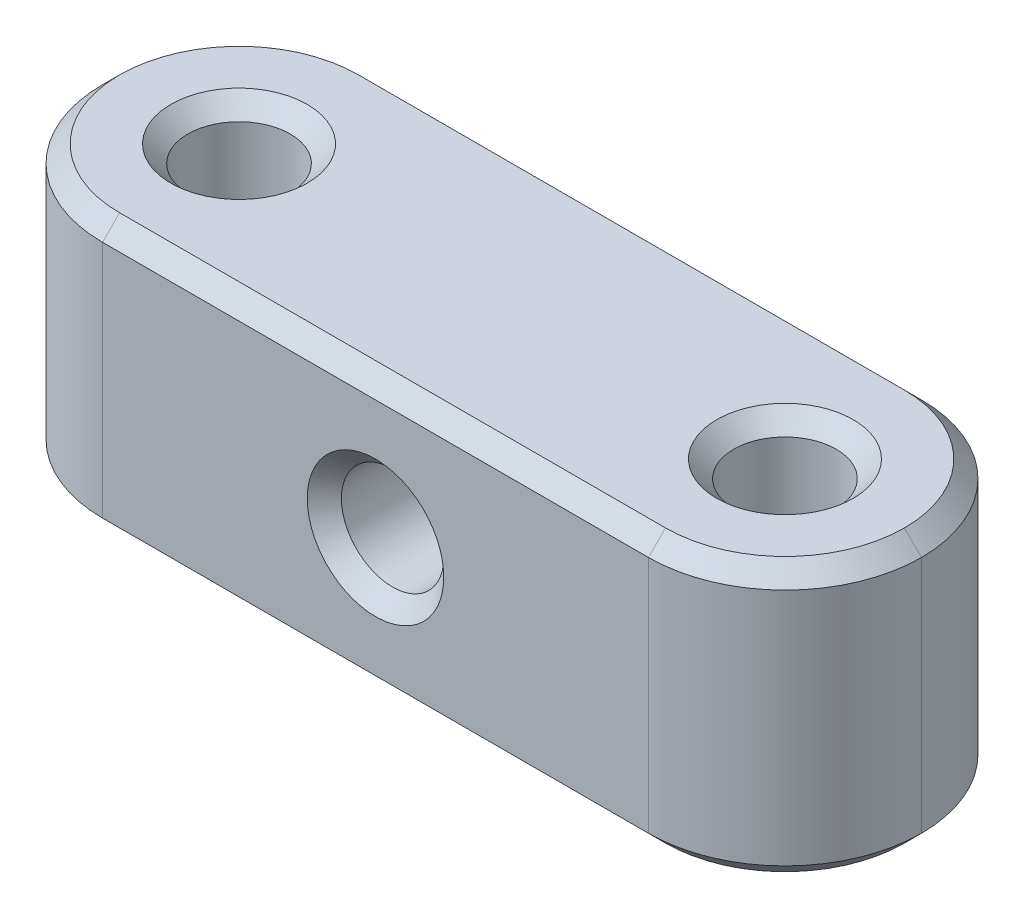
SolidWorks part; units mm, degrees
ref_plane "Front Plane" through (0, 0, 0) normal (0, 0, 1) x (1, 0, 0)
ref_plane "Top Plane" through (0, 0, 0) normal (0, 1, 0) x (1, 0, 0)
ref_plane "Right Plane" through (0, 0, 0) normal (1, 0, 0) x (0, 0, -1)
sketch "Sketch1" plane through (0, 0, 0) normal (0, 1, 0) x (1, 0, 0)
  line L1 (0, 0) -> (38.1, 0)
  line L2 (0, 0) -> (0, 12.7)
  line L3 (0, 12.7) -> (38.1, 12.7)
  line L4 (38.1, 0) -> (38.1, 12.7)
  circle A0 centre (6.35, 6.35) radius 2.3813
  circle A1 centre (31.75, 6.35) radius 2.3812
  dimension "D7" = 4.7625
  dimension "D8" = 4.7625
  dimension "D1" = 38.1
  dimension "D2" = 12.7
  dimension "D3" = 6.35
  dimension "D4" = 6.35
  dimension "D5" = 6.35
  dimension "D6" = 25.4
extrude "Boss-Extrude1" add sketch "Sketch1" along normal blind 12.7
sketch "Sketch2" plane through (0, 0, 0) normal (0, 0, 1) x (1, 0, 0)
  line L0 (0, 12.7) -> (0, 0) construction
  line L1 (0, 0) -> (38.1, 0) construction
  circle A0 centre (19.05, 6.35) radius 2.3813
  dimension "D3" = 4.7625
  dimension "D1" = 19.05
  dimension "D2" = 6.35
extrude "Cut-Extrude1" cut sketch "Sketch2" against normal through all both and the other way through all
fillet "Fillet2" radius 6.35 4 edges at (0, 6.35, -12.7) (0, 6.35, 0) (38.1, 6.35, -12.7) (38.1, 6.35, 0)
chamfer "Chamfer3" distance 0.7937 angle 45 18 edges at (16.6687, 6.35, 0) (21.4313, 6.35, -12.7) (31.75, 0, -3.9688) (19.05, 0, 0) (36.2401, 0, -1.8599) (36.2401, 0, -10.8401) (19.05, 0, -12.7) (1.8599, 0, -10.8401) (1.8599, 0, -1.8599) (6.35, 0, -3.9687) (31.75, 12.7, -3.9688) (6.35, 12.7, -3.9687) (36.2401, 12.7, -10.8401) (36.2401, 12.7, -1.8599) (19.05, 12.7, 0) (1.8599, 12.7, -1.8599) (1.8599, 12.7, -10.8401) (19.05, 12.7, -12.7)
